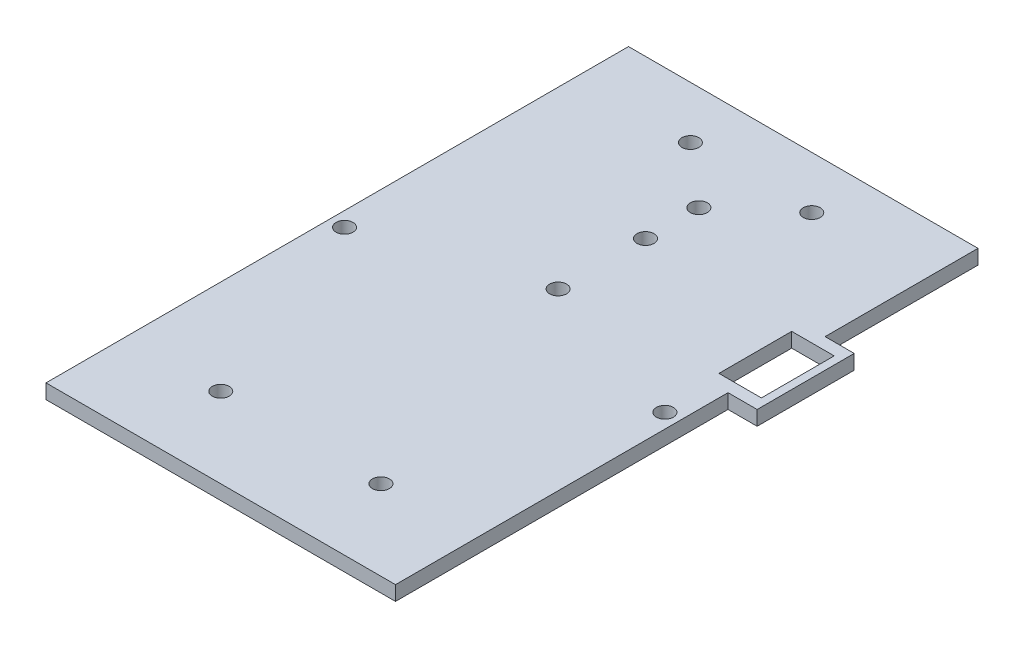
SolidWorks part; units mm, degrees
material "Acrylic (Medium-high impact)"
ref_plane "Front Plane" through (0, 0, 0) normal (0, 0, 1) x (1, 0, 0)
ref_plane "Top Plane" through (0, 0, 0) normal (0, 1, 0) x (1, 0, 0)
ref_plane "Right Plane" through (0, 0, 0) normal (1, 0, 0) x (0, 0, -1)
sketch "Sketch1" plane through (0, 0, 0) normal (0, 1, 0) x (1, 0, 0)
  line L0 (0, 0) -> (0, 50000) construction
  line L1 (36, -60) -> (-36, -60)
  line L2 (36, -60) -> (36, 60)
  line L3 (36, 60) -> (-36, 60)
  line L4 (-36, -60) -> (-36, 60)
  line L5 (36, -60) -> (-36, 60) construction
  line L6 (36, 60) -> (-36, -60) construction
  line L7 (0, 18.5) -> (36, 18.5) construction
  line L8 (0, 9.5) -> (0, -1.5)
  line L9 (0, 0) -> (50000, 0) construction
  line L10 (-20.7309, 49.25) -> (20.7309, 49.25) construction
  line L11 (30, 8.5) -> (42, 8.5)
  line L12 (30, 8.5) -> (30, 28.5)
  line L13 (30, 28.5) -> (42, 28.5)
  line L14 (42, 8.5) -> (42, 28.5)
  line L15 (30, 8.5) -> (42, 28.5) construction
  line L16 (30, 28.5) -> (42, 8.5) construction
  line L17 (40.375, 11) -> (31.625, 11)
  line L18 (40.375, 11) -> (40.375, 26)
  line L19 (40.375, 26) -> (31.625, 26)
  line L20 (31.625, 11) -> (31.625, 26)
  line L21 (40.375, 11) -> (31.625, 26) construction
  line L22 (40.375, 26) -> (31.625, 11) construction
  circle A0 centre (-33, -1.5) radius 1.75
  circle A1 centre (33, -1.5) radius 1.75
  circle A2 centre (-16.5, -43.5) radius 1.75
  circle A3 centre (16.5, -43.5) radius 1.75
  circle A4 centre (0, 27.5) radius 1.75
  circle A5 centre (0, 9.5) radius 1.75
  circle A10 centre (0, 38.5) radius 1.75
  circle A11 centre (0, 38.5) radius 1.75 construction
  circle A12 centre (-12.5, 49.25) radius 1.75
  circle A13 centre (12.5, 49.25) radius 1.75
  point P0 (0, 0)
  point P29 (36, 0)
  point P32 (36, 18.5)
  point P44 (0, 60)
  point P45 (0, 38.5)
  point P46 (0, 49.25)
  point P48 (0, 38.5)
  point P52 (0, 49.25)
  dimension "D3" = 3.5
  dimension "D4" = 3.5
  dimension "D5" = 33
  dimension "D6" = 3.5
  dimension "D7" = 3.5
  dimension "D10" = 3.5
  dimension "D11" = 3.5
  dimension "D15" = 20
  dimension "D16" = 12
  dimension "D17" = 15
  dimension "D19" = 66
  dimension "D12" = 9
  dimension "D20" = 3.5
  dimension "D21" = 3.5
  dimension "D1" = 120
  dimension "D2" = 72
  dimension "D8" = 42
  dimension "D9" = 16.5
  dimension "D13" = 18
  dimension "D14" = 11
  dimension "D18" = 8.75
  dimension "D22" = 25
extrude "Boss-Extrude1" add sketch "Sketch1" along normal blind 3 contours L12 L13 L2 L3 L4 L1 L11 A10 A5 A4 A3 A2 A1 A0 | L19 L18 L17 L2 L11 L14 L13 | L17 L20 L19 L2 L13 L12 L11 region at (-0.4696, 0, 0.3591) region at (33, 0, -8.7088) region at (36.2088, 0, -9.75)
